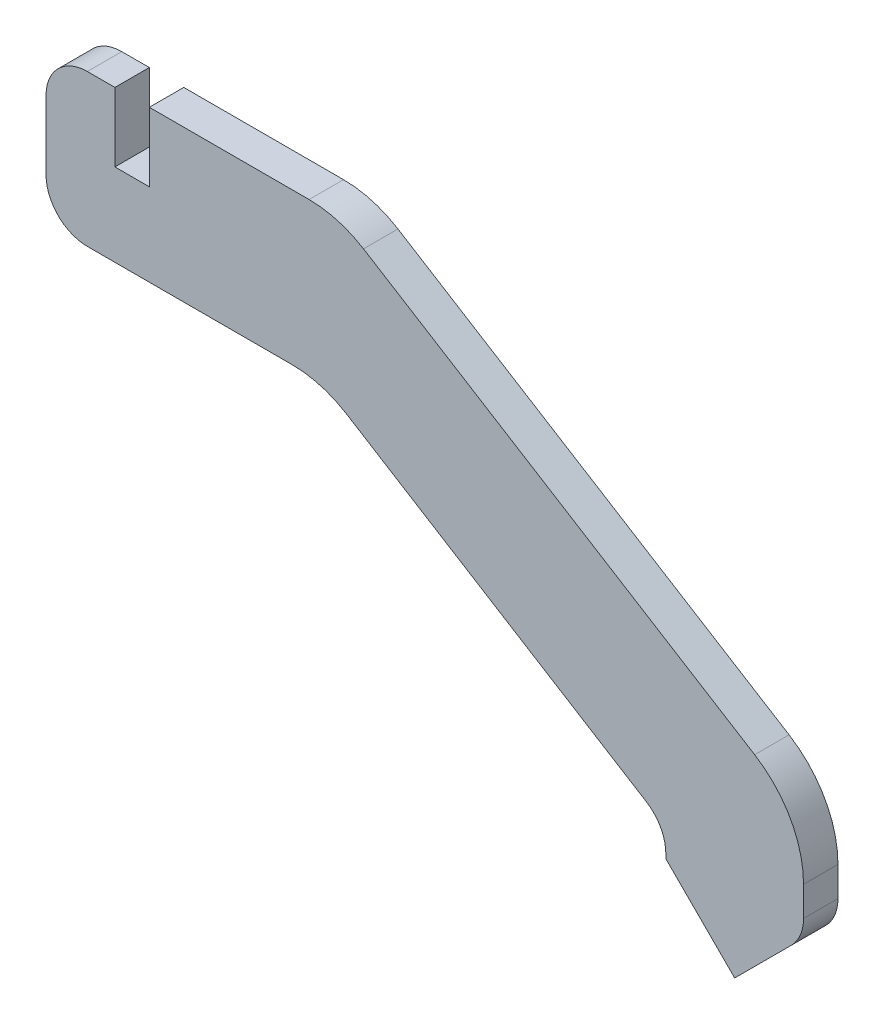
SolidWorks part; units mm, degrees
material "PBT General Purpose"
ref_plane "Front Plane" through (0, 0, 0) normal (0, 0, 1) x (1, 0, 0)
ref_plane "Top Plane" through (0, 0, 0) normal (0, 1, 0) x (1, 0, 0)
ref_plane "Right Plane" through (0, 0, 0) normal (1, 0, 0) x (0, 0, -1)
sketch "frame_outline" plane through (0, 0, 0) normal (0, 0, 1) x (1, 0, 0)
  line L127 (0, 0) -> (0, 1.1)
  line L128 (0, 1.1) -> (0.5, 1.1)
  line L129 (0.5, 1.1) -> (0.5, 0.6)
  line L130 (0.5, 0.6) -> (0.75, 0.6)
  line L131 (0.75, 0.6) -> (0.75, 1.1)
  line L132 (0.75, 1.1) -> (2.1236, 1.1)
  line L133 (2.1236, 1.1) -> (5.5, -0.9934)
  line L134 (5.5, -0.9934) -> (5.5, -1.75)
  line L135 (5.5, -1.75) -> (5, -2.25)
  line L136 (5, -2.25) -> (4.5, -1.75)
  line L137 (4.5, -1.75) -> (4.5, -1.55)
  line L138 (4.5, -1.55) -> (2, 0)
  line L139 (2, 0) -> (0, 0)
  dimension "D1" = 0.25
  dimension "D2" = 0.5
  dimension "D3" = 0.6
  dimension "D4" = 0.5
  dimension "D5" = 5
  dimension "D6" = 2.25
  dimension "D7" = 1
  dimension "D8" = 1
  dimension "D9" = 0.2
  dimension "D10" = 2
extrude "Boss-Extrude1" add sketch "frame_outline" along normal mid plane 0.25
fillet "Fillet1" radius 0.3 4 edges at (5.5, -1.75, 0) (0, 1.1, 0) (4.5, -1.55, 0) (0, 0, 0)
fillet "Fillet2" radius 0.75 3 edges at (5.5, -0.9934, 0) (2.1236, 1.1, 0) (2, 0, 0)
equation "\"t\"= 0.25'thickness of the sheets"
equation "\"t_cf\"= 0.115'thickness of single carbon fiber layer"
equation "\"t_kapton\"= 0.025'thickness of single Kapton flex layer"
equation "\"t_fr4\"= 0.1'thickness of FR4 with copper layer"
equation "\"joint_flex\"= 0.1'Width of flextures gap"
equation "\"joint_flex_eff\"= 0.02'Width of flecture after castelation"
equation "\"joint_fold\"= 0.2'Width of folding joints for 90deg fold"
equation "\"gap_tolerance\"= 0.002'Width to have interfecence fit between carbon fiber inserts"
equation "\"assemble_angle\"= 90'Angle of assembly parts"
equation "\"D1@Boss-Extrude1\"=\"t\""
equation "\"link_lift\"= 0.5'Actuation linkage amplification for the lift motion"
equation "\"link_swing\"= 0.45'Actuation linkage amplification for the swing motion"
equation "\"D1@frame_outline\"=\"t\""
